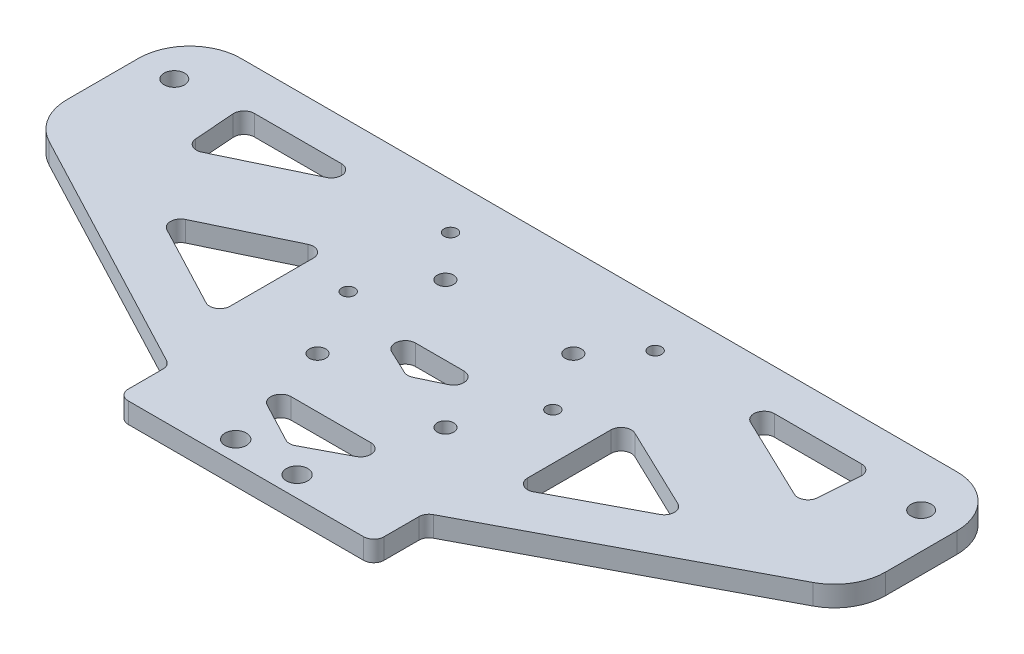
SolidWorks part; units mm, degrees
material "Thornel Mat VMA"
ref_plane "Front" through (0, 0, 0) normal (0, 0, 1) x (1, 0, 0)
ref_plane "Top" through (0, 0, 0) normal (0, 1, 0) x (1, 0, 0)
ref_plane "Right" through (0, 0, 0) normal (1, 0, 0) x (0, 0, -1)
sketch "草图1" plane through (0, 0, 0) normal (0, 1, 0) x (1, 0, 0)
  line L0 (0, 40.0348) -> (0, 0) construction
  line L1 (25, 0) -> (-25, 0)
  line L2 (-25, 0) -> (-80, 29)
  line L3 (-80, 29) -> (-80, 59)
  line L4 (-80, 59) -> (80, 59)
  line L5 (80, 29) -> (80, 59)
  line L6 (25, 0) -> (80, 29)
  point P9 (0, 59)
  dimension "D1" = 59
  dimension "D2" = 80
  dimension "D3" = 25
  dimension "D4" = 30
extrude "凸台-拉伸1" add sketch "草图1" along normal blind 4
sketch "草图2" plane through (0, 4, 0) normal (0, 1, 0) x (1, 0, 0)
  line L0 (0, 0) -> (0, 59) construction
  line L1 (80, 59) -> (-80, 59) construction
  line L2 (-12.5, 41.5) -> (-12.5, 16.5) construction
  line L3 (-12.5, 29) -> (12.5, 29) construction
  line L4 (12.5, 41.5) -> (12.5, 16.5) construction
  circle A0 centre (-12.5, 41.5) radius 1.6
  circle A3 centre (12.5, 41.5) radius 1.6
  circle A4 centre (-12.5, 16.5) radius 1.6
  circle A5 centre (12.5, 16.5) radius 1.6
  point P14 (0, 29)
  dimension "D1" = 3.2
  dimension "D2" = 25
  dimension "D4" = 17.5
  dimension "D3" = 12.5
extrude "切除-拉伸1" cut sketch "草图2" against normal through all
sketch "草图3" plane through (0, 4, 0) normal (0, 1, 0) x (1, 0, 0)
  line L0 (-80, 59) -> (-80, 29) construction
  line L1 (80, 59) -> (-80, 59) construction
  line L23 (-25, 0) -> (25, 0) construction
  line L24 (-66, 51.4654) -> (-66, 27.9182)
  line L25 (-65.4092, 27.0057) -> (-27.5283, 10.0199)
  line L26 (-26.3885, 11.6151) -> (-64.2694, 52.1482)
  line L27 (-56.7306, 52.8689) -> (-35.4528, 30.1014)
  line L28 (-33.7222, 30.7842) -> (-33.7222, 50.1473)
  line L29 (-34.5642, 51.1347) -> (-55.842, 54.5392)
  line L32 (-22.9874, 9.4403) -> (-26.732, 36.0544)
  line L33 (-80, 29) -> (-25, 0) construction
  line L34 (-13.5, 37) -> (-13.5, 17) construction
  line L35 (-28.7222, 35.9151) -> (-28.7222, 11.1733)
  line L36 (-28.1694, 10.2789) -> (-24.4249, 8.4066)
  line L37 (-13.5, 37) -> (-12.5, 41.5) construction
  line L38 (-4.3247, 7.5552) -> (-22.7222, 7.5552) construction
  line L39 (0, 30) -> (0, 0) construction
  line L40 (4.3247, 7.5552) -> (22.7222, 7.5552) construction
  line L41 (7.5, 20.5) -> (7.5, 10.5) construction
  line L42 (28.1694, 10.2789) -> (24.4249, 8.4066)
  line L43 (28.7222, 35.9151) -> (28.7222, 11.1733)
  line L44 (22.9874, 9.4403) -> (26.732, 36.0544)
  line L45 (34.5642, 51.1347) -> (55.842, 54.5392)
  line L46 (33.7222, 30.7842) -> (33.7222, 50.1473)
  line L47 (56.7306, 52.8689) -> (35.4528, 30.1014)
  line L48 (26.3885, 11.6151) -> (64.2694, 52.1482)
  line L49 (65.4092, 27.0057) -> (27.5283, 10.0199)
  line L50 (66, 51.4654) -> (66, 27.9182)
  line L51 (-12.5, 16.5) -> (-13.5, 17) construction
  circle A0 centre (-73, 51) radius 2.6
  arc A1 (-24.4249, 8.4066) -> (-22.9874, 9.4403) centre (-23.9777, 9.301) ccw
  arc A2 (-28.7222, 11.1733) -> (-28.1694, 10.2789) centre (-27.7222, 11.1733) ccw
  arc A3 (-28.7222, 35.9151) -> (-26.732, 36.0544) centre (-27.7222, 35.9151) cw
  arc A4 (-33.7222, 50.1473) -> (-34.5642, 51.1347) centre (-34.7222, 50.1473) ccw
  arc A5 (-56.7306, 52.8689) -> (-55.842, 54.5392) centre (-56, 53.5517) cw
  arc A6 (-35.4528, 30.1014) -> (-33.7222, 30.7842) centre (-34.7222, 30.7842) ccw
  arc A7 (-26.3885, 11.6151) -> (-27.5283, 10.0199) centre (-27.1191, 10.9323) cw
  arc A8 (-66, 27.9182) -> (-65.4092, 27.0057) centre (-65, 27.9182) ccw
  arc A9 (-66, 51.4654) -> (-64.2694, 52.1482) centre (-65, 51.4654) cw
  arc A10 (66, 51.4654) -> (64.2694, 52.1482) centre (65, 51.4654) ccw
  arc A11 (66, 27.9182) -> (65.4092, 27.0057) centre (65, 27.9182) cw
  arc A12 (26.3885, 11.6151) -> (27.5283, 10.0199) centre (27.1191, 10.9323) ccw
  arc A13 (35.4528, 30.1014) -> (33.7222, 30.7842) centre (34.7222, 30.7842) cw
  arc A14 (56.7306, 52.8689) -> (55.842, 54.5392) centre (56, 53.5517) ccw
  arc A15 (33.7222, 50.1473) -> (34.5642, 51.1347) centre (34.7222, 50.1473) cw
  arc A16 (28.7222, 35.9151) -> (26.732, 36.0544) centre (27.7222, 35.9151) ccw
  arc A17 (28.7222, 11.1733) -> (28.1694, 10.2789) centre (27.7222, 11.1733) cw
  arc A18 (24.4249, 8.4066) -> (22.9874, 9.4403) centre (23.9777, 9.301) cw
  circle A19 centre (73, 51) radius 2.6
  circle A20 centre (-13.5, 17) radius 1.6
  circle A21 centre (-13.5, 37) radius 1.6
  circle A22 centre (13.5, 17) radius 1.6
  circle A23 centre (13.5, 37) radius 1.6
  point P24 (-28.7222, 10.5552)
  point P32 (-28.7222, 50.2)
  point P35 (-33.7222, 51)
  point P38 (-58.7222, 55)
  point P43 (-23, 7.9894)
  point P46 (-66, 27.2707)
  point P49 (-66, 54)
  point P86 (66, 54)
  point P87 (66, 27.2707)
  point P88 (23, 7.9894)
  point P89 (58.7222, 55)
  point P90 (33.7222, 51)
  point P91 (28.7222, 50.2)
  point P92 (28.7222, 10.5552)
  dimension "D1" = 5.2
  dimension "D2" = 7
  dimension "D3" = 8
  dimension "D15" = 1
  dimension "D16" = 3.2
  dimension "D17" = 27
  dimension "D18" = 17
  dimension "D20" = 3.2
  dimension "D4" = 7
  dimension "D5" = 5
  dimension "D6" = 5
  dimension "D7" = 8
  dimension "D8" = 6
  dimension "D9" = 4
  dimension "D10" = 8
  dimension "D11" = 2
  dimension "D12" = 5
  dimension "D13" = 25
  dimension "D14" = 6
  dimension "D19" = 20
extrude "切除-拉伸2" [suppressed] cut sketch "草图3" against normal through all
fillet "圆角1" [suppressed] radius 7
sketch "草图4" plane through (0, 4, 0) normal (0, 1, 0) x (1, 0, 0)
  line L0 (0, 0) -> (0, 67.0073) construction
  line L1 (80, 59) -> (-80, 59) construction
  circle A0 centre (20, 50) radius 1.275
  circle A2 centre (20, 30) radius 1.275
  circle A3 centre (-20, 30) radius 1.275
  circle A4 centre (-20, 50) radius 1.275
  dimension "D1" = 2.55
  dimension "D2" = 20
  dimension "D4" = 9
  dimension "D5" = 20
  dimension "D3" = 2
extrude "切除-拉伸3" cut sketch "草图4" against normal blind 10
sketch "草图6" plane through (0, 4, 0) normal (0, 1, 0) x (1, 0, 0)
  line L1 (-25, 0) -> (25, 0)
  line L2 (-25, 0) -> (-25, -10)
  line L3 (-25, -10) -> (25, -10)
  line L4 (25, 0) -> (25, -10)
  dimension "D1" = 50
  dimension "D2" = 10
extrude "凸台-拉伸2" add sketch "草图6" against normal up to surface (4 mm away) up to face at (-20, 0, -51.275)
sketch "草图7" plane through (0, 4, 0) normal (0, 1, 0) x (1, 0, 0)
  line L0 (0, 0) -> (0, -33.3189) construction
  line L1 (-25, -10) -> (25, -10) construction
  circle A0 centre (-6, -6) radius 2.1
  circle A1 centre (6, -6) radius 2.1
  dimension "D1" = 4.2
  dimension "D2" = 6
  dimension "D3" = 4
extrude "切除-拉伸4" cut sketch "草图7" against normal blind 10
sketch "草图8" plane through (0, 4, 0) normal (0, 1, 0) x (1, 0, 0)
  line L0 (-80, 59) -> (-80, 29) construction
  line L1 (80, 59) -> (-80, 59) construction
  line L2 (0, 0) -> (0, 67.9824) construction
  circle A0 centre (-73, 49) radius 2
  circle A1 centre (73, 49) radius 2
  dimension "D1" = 4
  dimension "D2" = 7
  dimension "D3" = 10
extrude "切除-拉伸5" cut sketch "草图8" against normal blind 10
sketch "草图9" plane through (0, 4, 0) normal (0, 1, 0) x (1, 0, 0)
  line L0 (0, 0) -> (0, 79.7791) construction
  line L1 (-13.6072, 27.8756) -> (13.6072, 27.8756)
  line L2 (-13.6072, 27.8756) -> (0, 21.4248)
  line L3 (-61.5112, 51) -> (-33.5112, 51)
  line L4 (-33.5112, 51) -> (-60.5648, 38.0345)
  line L5 (-60.5648, 38.0345) -> (-61.5112, 51)
  line L6 (-51.7088, 24.599) -> (-29.0798, 35.444)
  line L7 (-29.0798, 35.444) -> (-29.0798, 12.6673)
  line L8 (-29.0798, 12.6673) -> (-51.7088, 24.599)
  line L9 (29.0798, 12.6673) -> (51.7088, 24.599)
  line L10 (29.0798, 35.444) -> (29.0798, 12.6673)
  line L11 (51.7088, 24.599) -> (29.0798, 35.444)
  line L12 (60.5648, 38.0345) -> (61.5112, 51)
  line L13 (33.5112, 51) -> (60.5648, 38.0345)
  line L14 (61.5112, 51) -> (33.5112, 51)
  line L15 (13.6072, 27.8756) -> (0, 21.4248)
  line L16 (80, 59) -> (-80, 59) construction
  line L17 (-80, 29) -> (-25, 0) construction
  line L18 (-80, 59) -> (-80, 29) construction
  point P19 (0, 27.8756)
  dimension "D1" = 28
  dimension "D2" = 8
  dimension "D3" = 13
  dimension "D4" = 30
extrude "切除-拉伸6" cut sketch "草图9" against normal blind 10
sketch "草图10" plane through (0, 4, 0) normal (0, 1, 0) x (1, 0, 0)
  line L0 (0, 0) -> (0, -26.7425) construction
  line L1 (0, 0) -> (0, 25.9451) construction
  line L2 (-15.8628, 6.6366) -> (15.8628, 6.6366)
  line L3 (15.8628, 6.6366) -> (0, -1.7274)
  line L4 (25, 0) -> (80, 29) construction
  line L5 (-15.8628, 6.6366) -> (0, -1.7274)
  point P11 (0, 6.6366)
extrude "切除-拉伸7" cut sketch "草图10" against normal blind 10
fillet "圆角2" radius 2 22 edges at (-25, 2, 0) (-25, 2, 10) (25, 2, 10) (25, 2, 0) (-13.6072, 2, -27.8756) (13.6072, 2, -27.8756) (0, 2, -21.4248) (-51.7088, 2, -24.599) (-29.0798, 2, -35.444) (-29.0798, 2, -12.6673) (-61.5112, 2, -51) (-33.5112, 2, -51) (-60.5648, 2, -38.0345) (33.5112, 2, -51) (61.5112, 2, -51) (60.5648, 2, -38.0345) (29.0798, 2, -35.444) (51.7088, 2, -24.599) (0, 2, 1.7274) (-15.8628, 2, -6.6366) (15.8628, 2, -6.6366) (29.0798, 2, -12.6673)
fillet "圆角3" radius 10 4 edges at (-80, 2, -29) (80, 2, -59) (80, 2, -29) (-80, 2, -59)
